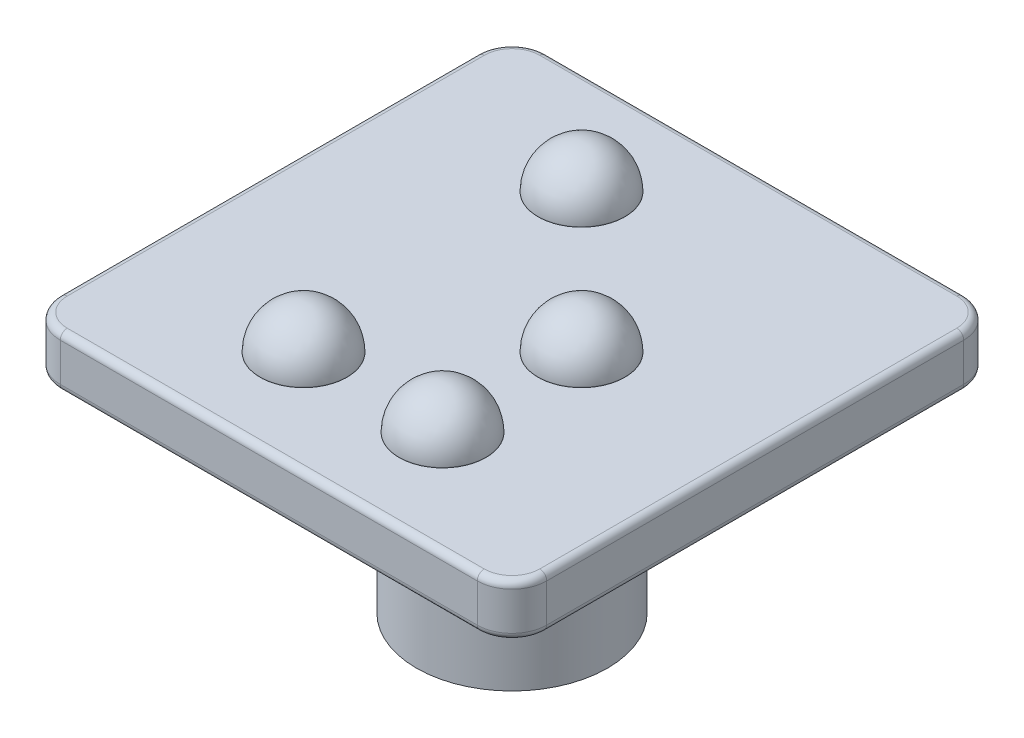
SolidWorks part; units mm, degrees
ref_plane "Front Plane" through (0, 0, 0) normal (0, 0, 1) x (1, 0, 0)
ref_plane "Top Plane" through (0, 0, 0) normal (0, 1, 0) x (1, 0, 0)
ref_plane "Right Plane" through (0, 0, 0) normal (1, 0, 0) x (0, 0, -1)
sketch "Sketch1" plane through (0, 0, 0) normal (0, 1, 0) x (1, 0, 0)
  line L1 (-7.3247, 4.3967) -> (4.6753, 4.3967)
  line L2 (-8.3247, 3.3967) -> (-8.3247, -8.6033)
  line L3 (-7.3247, -9.6033) -> (4.6753, -9.6033)
  line L4 (5.6753, 3.3967) -> (5.6753, -8.6033)
  arc A0 (-8.3247, -8.6033) -> (-7.3247, -9.6033) centre (-7.3247, -8.6033) ccw
  arc A1 (4.6753, -9.6033) -> (5.6753, -8.6033) centre (4.6753, -8.6033) ccw
  arc A2 (4.6753, 4.3967) -> (5.6753, 3.3967) centre (4.6753, 3.3967) cw
  arc A3 (-7.3247, 4.3967) -> (-8.3247, 3.3967) centre (-7.3247, 3.3967) ccw
  point P8 (5.6753, -9.6033)
  point P11 (5.6753, 4.3967)
  point P14 (-8.3247, 4.3967)
  dimension "D3" = 1
  dimension "D1" = 14
  dimension "D2" = 14
extrude "Boss-Extrude1" add sketch "Sketch1" along normal blind 1.5
sketch "Sketch2" plane through (0, 0, 0) normal (0, -1, 0) x (1, 0, 0)
  line L0 (-7.3247, 9.6033) -> (4.6753, 9.6033) construction
  line L1 (5.6753, 8.6033) -> (5.6753, -3.3967) construction
  line L2 (-1.3247, -4.3967) -> (-1.3247, 9.6033) construction
  line L3 (-8.3247, 2.6033) -> (5.6753, 2.6033) construction
  line L4 (-8.3247, -3.3967) -> (-8.3247, 8.6033) construction
  circle A0 centre (-1.3247, 2.6033) radius 2.75
  dimension "D1" = 7
  dimension "D2" = 7
extrude "Boss-Extrude2" add sketch "Sketch2" along normal blind 6
sketch "Sketch3" plane through (0, -6, 0) normal (0, -1, 0) x (1, 0, 0)
  line L0 (-1.3247, 5.3533) -> (-1.3247, -0.1467) construction
  line L1 (-3.3247, 3.1533) -> (0.6753, 3.1533)
  line L2 (-3.3247, 3.1533) -> (-3.3247, 2.0533)
  line L3 (-3.3247, 2.0533) -> (0.6753, 2.0533)
  line L4 (0.6753, 3.1533) -> (0.6753, 2.0533)
  line L5 (-1.8747, 4.6033) -> (-0.7747, 4.6033)
  line L6 (-1.8747, 4.6033) -> (-1.8747, 0.6033)
  line L7 (-1.8747, 0.6033) -> (-0.7747, 0.6033)
  line L8 (-0.7747, 4.6033) -> (-0.7747, 0.6033)
  line L9 (-4.0747, 2.6033) -> (1.4253, 2.6033) construction
  circle A3 centre (-1.3247, 2.6033) radius 2.75 construction
  circle A4 centre (-1.3247, 2.6033) radius 2.75 construction
  dimension "D7" = 0.55
  dimension "D1" = 4
  dimension "D2" = 1.1
  dimension "D3" = 1.1
  dimension "D4" = 4
  dimension "D8" = 0.55
extrude "Cut-Extrude1" cut sketch "Sketch3" against normal blind 6 contours L8 L5 L6 L1 | L1 L8 L3 L4 | L8 L1 L6 L3 | L6 L1 L2 L3 | L8 L3 L6 L7 region at (-2.5997, -6, 2.6033) region at (-1.3247, -6, 3.8783) region at (-1.3247, -6, 2.6033) region at (-0.0497, -6, 2.6033) region at (-1.3247, -6, 1.3283)
chamfer "Chamfer1" distance 0.3 angle 45 12 edges at (-1.3247, -6, 0.6033) (-1.8747, -6, 1.3283) (-2.5997, -6, 2.0533) (-3.3247, -6, 2.6033) (-2.5997, -6, 3.1533) (-0.7747, -6, 1.3283) (-0.0497, -6, 2.0533) (0.6753, -6, 2.6033) (-0.0497, -6, 3.1533) (-0.7747, -6, 3.8783) (-1.3247, -6, 4.6033) (-1.8747, -6, 3.8783)
fillet "Fillet1" radius 1 1 edges at (-1.3247, 0, -0.1467)
sketch "Sketch4" plane through (0, 1.5, 0) normal (0, 1, 0) x (1, 0, 0)
  line L0 (-1.3247, 4.3967) -> (-1.3247, -9.6033) construction
  line L1 (4.6753, 4.3967) -> (-7.3247, 4.3967) construction
  line L2 (-7.3247, -9.6033) -> (4.6753, -9.6033) construction
  line L3 (5.6753, -2.6033) -> (-8.3247, -2.6033) construction
  line L4 (-8.3247, 3.3967) -> (-8.3247, -8.6033) construction
  line L5 (5.6753, -8.6033) -> (5.6753, 3.3967) construction
  line L6 (-3.3247, 4.3967) -> (-3.3247, -9.6033) construction
  line L7 (0.6753, 4.3967) -> (0.6753, -9.6033) construction
  line L8 (-8.3247, 1.3967) -> (5.6753, 1.3967) construction
  line L9 (5.6753, -6.6033) -> (-8.3247, -6.6033) construction
  circle A0 centre (-3.3247, 1.3967) radius 1.25
  circle A1 centre (0.6753, -2.6033) radius 1.25
  circle A3 centre (-3.3247, -6.6033) radius 1.25
  circle A4 centre (0.6753, -6.6033) radius 1.25
  dimension "D1" = 4
  dimension "D2" = 4
  dimension "D3" = 2
  dimension "D4" = 2
extrude "Boss-Extrude3" add sketch "Sketch4" along normal blind 0.01
dome "Dome1" faces to dome 1 distance 1.25 reverse direction no elliptical dome no face at (-3.3247, 1.51, -0.1467) parameters "D1"=1.25
dome "Dome4" faces to dome 1 distance 1.25 reverse direction no elliptical dome no face at (0.6753, 1.51, 3.8533) parameters "D1"=1.25
dome "Dome5" faces to dome 1 distance 1.25 reverse direction no elliptical dome no face at (-3.3247, 1.51, 7.8533) parameters "D1"=1.25
dome "Dome6" faces to dome 1 distance 1.25 reverse direction no elliptical dome no face at (0.6753, 1.51, 7.8533) parameters "D1"=1.25
fillet "Fillet3" radius 0.2 16 edges at (5.3824, 1.5, -4.1038) (5.6753, 1.5, 2.6033) (5.3824, 1.5, 9.3104) (-1.3247, 1.5, 9.6033) (-8.0318, 1.5, 9.3104) (-8.0318, 1.5, -4.1038) (-8.3247, 1.5, 2.6033) (-1.3247, 1.5, -4.3967) (5.3824, 0, 9.3104) (5.6753, 0, 2.6033) (5.3824, 0, -4.1038) (-1.3247, 0, -4.3967) (-8.0318, 0, -4.1038) (-8.3247, 0, 2.6033) (-8.0318, 0, 9.3104) (-1.3247, 0, 9.6033)
